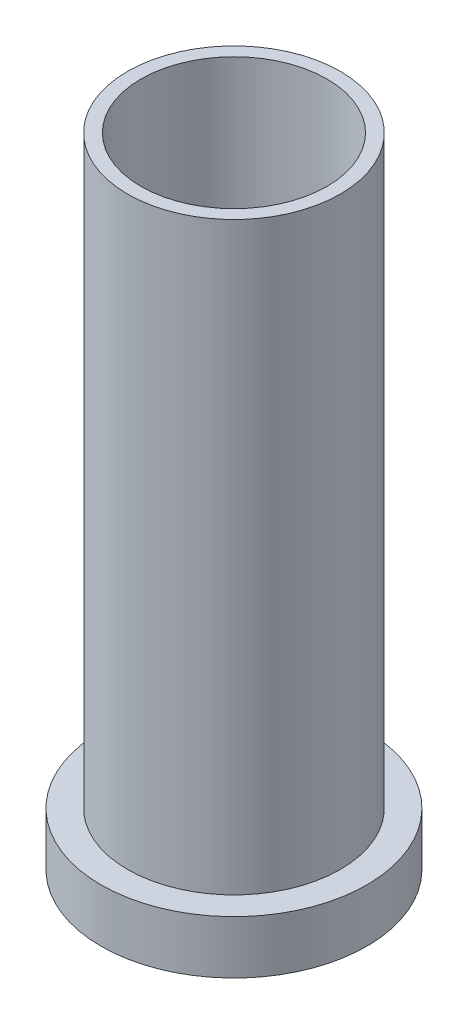
SolidWorks part; units mm, degrees
ref_plane "Front Plane" through (0, 0, 0) normal (0, 0, 1) x (1, 0, 0)
ref_plane "Top Plane" through (0, 0, 0) normal (0, 1, 0) x (1, 0, 0)
ref_plane "Right Plane" through (0, 0, 0) normal (1, 0, 0) x (0, 0, -1)
sketch "Sketch2" plane through (0, 0, 0) normal (0, 1, 0) x (1, 0, 0)
  circle A0 centre (0, 0) radius 44.45
  circle A1 centre (0, 0) radius 50.8
  dimension "D1" = 101.6
  dimension "D2" = 88.9
extrude "Boss-Extrude1" add sketch "Sketch2" along normal blind 304.8
sketch "Sketch4" plane through (0, 0, 0) normal (0, 1, 0) x (1, 0, 0)
  circle A0 centre (0, 0) radius 63.5
  circle A1 centre (0, 0) radius 44.45
  dimension "D1" = 127
extrude "Boss-Extrude3" add sketch "Sketch4" along normal blind 25.4
